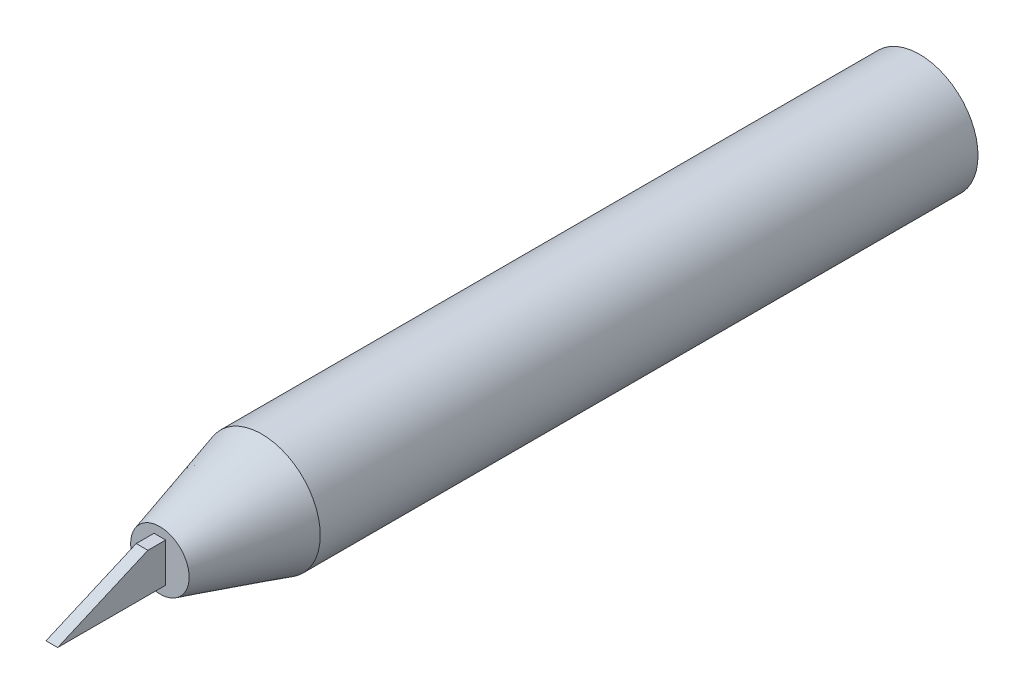
SolidWorks part; units mm, degrees
ref_plane "Front Plane" through (0, 0, 0) normal (0, 0, 1) x (1, 0, 0)
ref_plane "Top Plane" through (0, 0, 0) normal (0, 1, 0) x (1, 0, 0)
ref_plane "Right Plane" through (0, 0, 0) normal (1, 0, 0) x (0, 0, -1)
sketch "Sketch1" plane through (0, 0, 0) normal (0, 0, 1) x (1, 0, 0)
  circle A0 centre (-32.5, -25) radius 1
extrude "Boss-Extrude1" add sketch "Sketch1" along normal blind 3 and the other way blind 10 contours A0
chamfer "Chamfer1" distance 0.5 angle 74 1 edges at (-31.5, -25, 3) first distance on face at (-31.5, -25, 3)
ref_plane "Plane1" through (-32.5, 0, 0) normal (-1, 0, 0) x (0, 0, 1)
sketch "Sketch2" plane through (-32.5, 0, 0) normal (-1, 0, 0) x (0, 0, 1)
  line L0 (1.4716, -25.3178) -> (4.849, -25.3178)
  line L1 (4.849, -25.3178) -> (3.3055, -24.6485)
  line L2 (3.3055, -24.6485) -> (1.4716, -24.6485)
  line L3 (1.4716, -24.6485) -> (1.4716, -25.3178)
extrude "Boss-Extrude2" add sketch "Sketch2" along normal blind 0.1 and the other way blind 0.1 contours L0 L1 L2 L3
